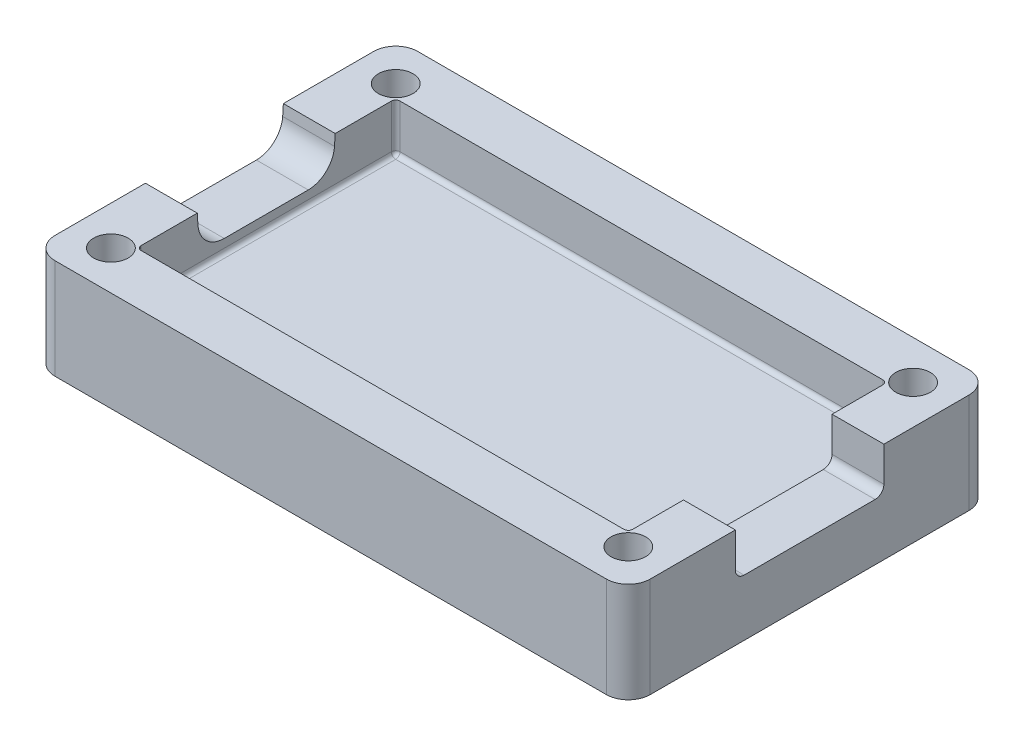
SolidWorks part; units mm, degrees
material "ABS"
ref_plane "Front Plane" through (0, 0, 0) normal (0, 0, 1) x (1, 0, 0)
ref_plane "Top Plane" through (0, 0, 0) normal (0, 1, 0) x (1, 0, 0)
ref_plane "Right Plane" through (0, 0, 0) normal (1, 0, 0) x (0, 0, -1)
sketch "Sketch1" plane through (0, 0, 0) normal (0, 1, 0) x (1, 0, 0)
  line L1 (-17.224, -10.493) -> (17.224, -10.493)
  line L2 (-17.224, -10.493) -> (-17.224, 10.493)
  line L3 (-17.224, 10.493) -> (17.224, 10.493)
  line L4 (17.224, -10.493) -> (17.224, 10.493)
  line L5 (-17.224, -10.493) -> (17.224, 10.493) construction
  line L6 (-17.224, 10.493) -> (17.224, -10.493) construction
  point P0 (0, 0)
  dimension "D1" = 20.986
  dimension "D2" = 34.448
extrude "Boss-Extrude1" add sketch "Sketch1" along normal blind 5.794
sketch "Sketch2" plane through (0, 5.794, 0) normal (0, 1, 0) x (1, 0, 0)
  line L1 (-14.224, -7.493) -> (14.224, -7.493)
  line L2 (-14.224, -7.493) -> (-14.224, 7.493)
  line L3 (-14.224, 7.493) -> (14.224, 7.493)
  line L4 (14.224, -7.493) -> (14.224, 7.493)
  line L5 (-14.224, -7.493) -> (14.224, 7.493) construction
  line L6 (-14.224, 7.493) -> (14.224, -7.493) construction
  point P0 (0, 0)
  dimension "D1" = 14.986
  dimension "D2" = 28.448
extrude "Cut-Extrude1" cut sketch "Sketch2" against normal blind 2.794
fillet "Fillet4" radius 0.254 4 edges at (14.224, 4.397, 7.493) (-14.224, 4.397, 7.493) (14.224, 4.397, -7.493) (-14.224, 4.397, -7.493)
sketch "Sketch3" plane through (17.224, 0, 0) normal (1, 0, 0) x (0, 0, -1)
  line L0 (-10.493, 5.794) -> (10.493, 5.794) construction
  line L1 (-4.2995, 5.794) -> (4.2995, 5.794)
  line L2 (-4.2995, 5.794) -> (-4.2995, 3.2749)
  line L3 (-4.2995, 3.2749) -> (4.2995, 3.2749)
  line L4 (4.2995, 5.794) -> (4.2995, 3.2749)
  line L5 (-10.493, 0) -> (10.493, 0) construction
  point P6 (0, 3.2749)
  point P11 (0, 0)
extrude "Cut-Extrude2" cut sketch "Sketch3" against normal up to surface (3 mm away) up to face at (14.224, 4.397, 0)
sketch "Sketch5" plane through (-17.224, 0, 0) normal (-1, 0, 0) x (0, 0, 1)
  line L0 (-3.9914, 5.794) -> (3.9914, 5.794)
  line L1 (-10.493, 5.794) -> (10.493, 5.794) construction
  line L2 (-10.493, 0) -> (10.493, 0) construction
  line L3 (-3.8587, 3.7446) -> (3.8587, 3.7446)
  line L4 (3.8587, 3.7446) -> (3.9914, 5.794)
  line L5 (-3.9914, 5.794) -> (-3.8587, 3.7446)
  point P4 (0, 5.794)
  point P7 (0, 0)
  point P8 (0, 3.7446)
  point P11 (3.8587, 3.7446)
extrude "Cut-Extrude3" cut sketch "Sketch5" against normal up to surface (3 mm away) up to face at (-14.224, 4.397, 0)
fillet "Fillet1" radius 1.524 2 edges at (-15.724, 3.7446, 3.8587) (-15.724, 3.7446, -3.8587)
fillet "Fillet2" radius 0.508 2 edges at (15.724, 3.2749, -4.2995) (15.724, 3.2749, 4.2995)
fillet "Fillet3" radius 1.27 4 edges at (-17.224, 2.897, -10.493) (-17.224, 2.897, 10.493) (17.224, 2.897, 10.493) (17.224, 2.897, -10.493)
sketch "Sketch7" plane through (0, 0, 0) normal (0, -1, 0) x (1, 0, 0)
  line L0 (-16.852, -10.121) -> (-14.1496, -7.4186) construction
  line L5 (-15.954, 10.493) -> (15.954, 10.493) construction
  line L9 (-14.9721, -8.2411) -> (14.9721, -8.2411) construction
  line L10 (-14.9721, -8.2411) -> (-14.9721, 8.2411) construction
  line L11 (-14.9721, 8.2411) -> (14.9721, 8.2411) construction
  line L12 (14.9721, -8.2411) -> (14.9721, 8.2411) construction
  line L13 (-14.9721, -8.2411) -> (14.9721, 8.2411) construction
  line L14 (-14.9721, 8.2411) -> (14.9721, -8.2411) construction
  circle A0 centre (-14.9721, 8.2411) radius 2
  circle A1 centre (14.9721, 8.2411) radius 2
  circle A2 centre (14.9721, -8.2411) radius 2
  circle A3 centre (-14.9721, -8.2411) radius 2
  arc A4 (-14.224, -7.239) -> (-13.97, -7.493) centre (-13.97, -7.239) ccw construction
  arc A5 (-17.224, -9.223) -> (-15.954, -10.493) centre (-15.954, -9.223) ccw construction
  point P0 (0, 0)
  point P4 (0, 0)
  point P10 (0, 0)
  point P19 (-14.1496, -7.4186)
  point P20 (0, 0)
  point P25 (-16.852, -10.121)
  dimension "D1" = 4
extrude "Cut-Extrude4" cut sketch "Sketch7" against normal blind 2
sketch "Sketch9" plane through (0, 0, 0) normal (0, -1, 0) x (1, 0, 0)
  circle A0 centre (-14.9721, 8.2411) radius 1
  circle A1 centre (-14.9721, 8.2411) radius 2 construction
  circle A2 centre (14.9721, 8.2411) radius 1
  circle A3 centre (14.9721, -8.2411) radius 1
  circle A4 centre (-14.9721, -8.2411) radius 1
  circle A5 centre (14.9721, 8.2411) radius 2 construction
  circle A6 centre (14.9721, -8.2411) radius 2 construction
  circle A7 centre (-14.9721, -8.2411) radius 2 construction
  dimension "D1" = 2
extrude "Cut-Extrude5" cut sketch "Sketch9" against normal through all
fillet "Fillet5" radius 0.254 8 edges at (-14.1496, 3, 7.4186) (-14.224, 3, 0) (-14.1496, 3, -7.4186) (0, 3, -7.493) (14.1496, 3, -7.4186) (14.224, 3, 0) (14.1496, 3, 7.4186) (0, 3, 7.493)
equation "\"width\"=0.59"
equation "\"D1@Sketch2\"=\"width\""
equation "\"D1@Sketch1\"=\"width\"+6mm"
equation "\"height\"=1.12"
equation "\"D2@Sketch2\"=\"height\""
equation "\"D2@Sketch1\"=\"height\" + 6mm"
